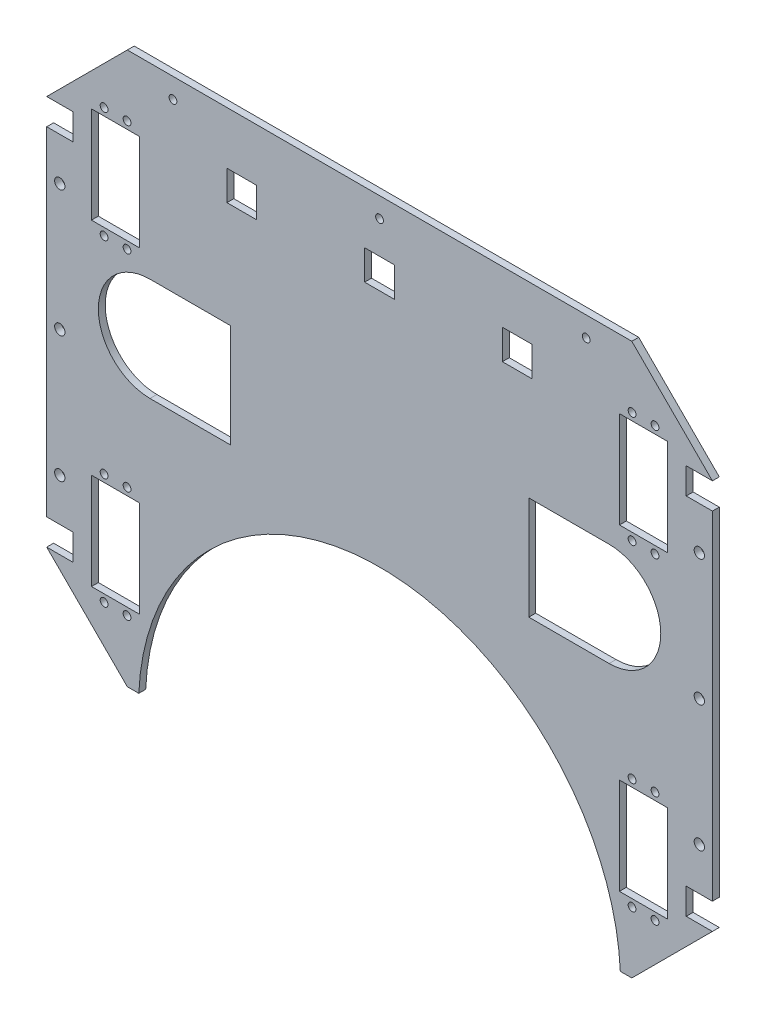
SolidWorks part; units mm, degrees
ref_plane "Plan de face" through (0, 0, 0) normal (0, 0, 1) x (1, 0, 0)
ref_plane "Plan de dessus" through (0, 0, 0) normal (0, 1, 0) x (1, 0, 0)
ref_plane "Plan de droite" through (0, 0, 0) normal (1, 0, 0) x (0, 0, -1)
sketch "Esquisse1" plane through (0, 0, 0) normal (0, 0, 1) x (1, 0, 0)
  line L0 (-145, 85) -> (-109.8862, 120.1138)
  line L1 (-109.8862, 120.1138) -> (-105, 125) construction
  line L2 (109.8862, 120.1138) -> (145, 85)
  line L3 (-85, 145) -> (85, 145) construction
  line L4 (105, -125) -> (109.8862, -120.1138) construction
  line L5 (-145, -145) -> (145, 145) construction
  line L6 (-145, 145) -> (145, -145) construction
  line L7 (85, 145) -> (105, 125) construction
  line L8 (-105, -125) -> (-85, -145) construction
  line L9 (-105, -125) -> (105, -125) construction
  line L10 (-105, 125) -> (105, 125) construction
  line L11 (85, -145) -> (105, -125) construction
  line L12 (-105, 125) -> (-85, 145) construction
  line L13 (105, 125) -> (109.8862, 120.1138) construction
  line L14 (-85, -145) -> (85, -145) construction
  line L15 (-109.8862, -120.1138) -> (-105, -125) construction
  line L16 (-109.8862, 120.1138) -> (109.8862, 120.1138)
  line L18 (-145, 0) -> (145, 0) construction
  line L19 (145, 85) -> (145, -85)
  line L20 (104.8862, -120.1138) -> (109.8862, -120.1138)
  line L21 (-109.8862, -120.1138) -> (-104.8862, -120.1138)
  line L22 (-145, 85) -> (-145, -85)
  line L24 (109.8862, -120.1138) -> (145, -85)
  line L25 (-145, -85) -> (-109.8862, -120.1138)
  line L28 (0, 125) -> (0, -125) construction
  arc A1 (-104.8862, -120.1138) -> (104.8862, -120.1138) centre (0, -125) cw
  point P0 (0, 0)
  point P30 (-145, 0)
  dimension "D1" = 290
  dimension "D2" = 290
  dimension "D6" = 60
  dimension "D7" = 60
extrude "Boss.-Extru.1" add sketch "Esquisse1" along normal blind 3
sketch "Esquisse21" plane through (0, 0, 3) normal (0, 0, 1) x (1, 0, 0)
  line L0 (0, 0) -> (191.7599, 0) construction
  line L1 (-145, 85) -> (-133.6, 85)
  line L2 (-145, 85) -> (-145, 73.6)
  line L3 (-145, 73.6) -> (-133.6, 73.6)
  line L4 (-133.6, 85) -> (-133.6, 73.6)
  line L5 (0, 0) -> (0, 158.3492) construction
  line L6 (145, 85) -> (145, 73.6)
  line L7 (145, 73.6) -> (133.6, 73.6)
  line L8 (133.6, 85) -> (133.6, 73.6)
  line L9 (145, 85) -> (133.6, 85)
  line L10 (-133.6, -85) -> (-133.6, -73.6)
  line L11 (-145, -73.6) -> (-133.6, -73.6)
  line L12 (-145, -85) -> (-145, -73.6)
  line L13 (-145, -85) -> (-133.6, -85)
  line L14 (145, -85) -> (145, -73.6)
  line L15 (145, -85) -> (133.6, -85)
  line L16 (145, -73.6) -> (133.6, -73.6)
  line L17 (133.6, -85) -> (133.6, -73.6)
  point P5 (-139.3, 79.3)
  point P9 (139.3, 79.3)
  point P19 (-139.3, -79.3)
  point P23 (139.3, -79.3)
  dimension "D1" = 11.4
  dimension "D2" = 11.4
  dimension "D3" = 5.7
  dimension "D4" = 5.7
sketch "Esquisse26" plane through (0, 0, 3) normal (0, 0, 1) x (1, 0, 0)
  line L0 (109.8862, 120.1138) -> (-109.8862, 120.1138) construction
  line L1 (-125.5, -48.1138) -> (-104.5, -48.1138)
  line L2 (-125.5, -48.1138) -> (-125.5, -90.1138)
  line L3 (-125.5, -90.1138) -> (-104.5, -90.1138)
  line L4 (-104.5, -48.1138) -> (-104.5, -90.1138)
  line L5 (-125.5, -48.1138) -> (-104.5, -90.1138) construction
  line L6 (-125.5, -90.1138) -> (-104.5, -48.1138) construction
  line L7 (145, -85) -> (145, 85) construction
  line L8 (-145, 85) -> (-145, -85) construction
  line L9 (-109.8862, -120.1138) -> (-104.8862, -120.1138) construction
  line L10 (104.8862, -120.1138) -> (109.8862, -120.1138) construction
  line L11 (-125.5, 90.1138) -> (-104.5, 90.1138)
  line L12 (-125.5, 90.1138) -> (-125.5, 48.1138)
  line L13 (-125.5, 48.1138) -> (-104.5, 48.1138)
  line L14 (-104.5, 90.1138) -> (-104.5, 48.1138)
  line L15 (-125.5, 90.1138) -> (-104.5, 48.1138) construction
  line L16 (-125.5, 48.1138) -> (-104.5, 90.1138) construction
  line L17 (104.5, 90.1138) -> (125.5, 90.1138)
  line L18 (104.5, 90.1138) -> (104.5, 48.1138)
  line L19 (104.5, 48.1138) -> (125.5, 48.1138)
  line L20 (125.5, 90.1138) -> (125.5, 48.1138)
  line L21 (104.5, 90.1138) -> (125.5, 48.1138) construction
  line L22 (104.5, 48.1138) -> (125.5, 90.1138) construction
  line L23 (104.5, -48.1138) -> (125.5, -48.1138)
  line L24 (104.5, -48.1138) -> (104.5, -90.1138)
  line L25 (104.5, -90.1138) -> (125.5, -90.1138)
  line L26 (125.5, -48.1138) -> (125.5, -90.1138)
  line L27 (104.5, -48.1138) -> (125.5, -90.1138) construction
  line L28 (104.5, -90.1138) -> (125.5, -48.1138) construction
  point P0 (-115, -69.1138)
  point P9 (-115, 69.1138)
  point P14 (115, 69.1138)
  point P19 (115, -69.1138)
  dimension "D1" = 30
  dimension "D2" = 30
  dimension "D3" = 42
  dimension "D4" = 21
  dimension "D5" = 30
  dimension "D6" = 30
  dimension "D7" = 42
  dimension "D8" = 21
  dimension "D9" = 30
  dimension "D10" = 30
  dimension "D11" = 42
  dimension "D12" = 21
  dimension "D13" = 21
  dimension "D14" = 42
  dimension "D15" = 30
  dimension "D16" = 30
extrude "Enlèv. mat.-Extru.1" cut sketch "Esquisse26" against normal through all
extrude "Enlèv. mat.-Extru.3" cut sketch "Esquisse21" against normal through all
sketch "Esquisse27" plane through (0, 0, 3) normal (0, 0, 1) x (1, 0, 0)
  line L0 (0, 120.1138) -> (0, -20) construction
  line L1 (109.8862, 120.1138) -> (-109.8862, 120.1138) construction
  line L2 (-145, 0) -> (145, 0) construction
  line L3 (-115, 90.1138) -> (-115, 48.1138) construction
  line L4 (-104.5, 90.1138) -> (-125.5, 90.1138) construction
  line L5 (-125.5, 48.1138) -> (-104.5, 48.1138) construction
  line L6 (-145, 73.6) -> (-145, -73.6) construction
  line L7 (145, -73.6) -> (145, 73.6) construction
  line L8 (-104.5, 48.1138) -> (-104.5, 90.1138) construction
  line L9 (-125.5, 90.1138) -> (-125.5, 48.1138) construction
  line L10 (-125.5, 69.1138) -> (-104.5, 69.1138) construction
  arc A0 (104.8862, -120.1138) -> (-104.8862, -120.1138) centre (0, -125) ccw construction
  point P0 (-120, 93.3138)
  point P1 (-110, 93.3138)
  point P2 (-120, 44.9138)
  point P3 (-110, 44.9138)
  point P29 (110, 44.9138)
  point P30 (120, 44.9138)
  point P31 (110, 93.3138)
  point P32 (120, 93.3138)
  point P33 (110, -44.9138)
  point P34 (120, -44.9138)
  point P35 (120, -93.3138)
  point P36 (110, -93.3138)
  point P37 (-110, -44.9138)
  point P38 (-120, -44.9138)
  point P39 (-110, -93.3138)
  point P40 (-120, -93.3138)
  dimension "D1" = 10
  dimension "D2" = 5
  dimension "D3" = 10
  dimension "D4" = 5
  dimension "D5" = 24.2
  dimension "D6" = 24.2
  dimension "D7" = 24.2
  dimension "D8" = 24.2
hole_wizard "Dégagement M32" positions "Esquisse31" profile "Esquisse30" hole size "M3" standard "ISO" end condition through all
sketch "Esquisse31" plane through (0, 0, 3) normal (0, 0, 1) x (1, 0, 0)
  point P1 (-120, 93.3138)
  point P4 (-110, 93.3138)
  point P7 (-120, 44.9138)
  point P10 (-110, 44.9138)
  point P13 (-120, -44.9138)
  point P16 (-110, -44.9138)
  point P19 (-120, -93.3138)
  point P22 (-110, -93.3138)
  point P25 (110, -93.3138)
  point P28 (120, -93.3138)
  point P31 (120, -44.9138)
  point P34 (110, -44.9138)
  point P37 (120, 44.9138)
  point P40 (110, 44.9138)
  point P43 (110, 93.3138)
  point P46 (120, 93.3138)
sketch "Esquisse30" plane through (-120, 93.3138, 3) normal (1, 0, 0) x (0, -1, 0)
  line L0 (0, 0) -> (0, 3)
  line L1 (0, 3) -> (1.7, 3)
  line L2 (1.7, 3) -> (1.7, 0)
  line L5 (1.7, 0) -> (0, 0)
  line L11 (0, -6.35) -> (0, 107.95) construction
  dimension "Diamètre du perçage jusqu'au prochain" = 3.4
  dimension "Profondeur du perçage jusqu'au prochain" = 3
sketch "Esquisse32" plane through (0, 0, 3) normal (0, 0, 1) x (1, 0, 0)
  line L0 (-118.5862, 111.4138) -> (118.5862, 111.4138) construction
  line L1 (-109.8862, 120.1138) -> (-145, 85) construction
  line L2 (145, 85) -> (109.8862, 120.1138) construction
  line L3 (-145, 73.6) -> (-133.6, 73.6) construction
  line L4 (-139.3, 73.6) -> (-139.3, -73.6) construction
  line L5 (-133.6, -73.6) -> (-145, -73.6) construction
  line L6 (139.3, 73.6) -> (139.3, -73.6) construction
  line L7 (133.6, 73.6) -> (145, 73.6) construction
  line L9 (109.8862, 120.1138) -> (-109.8862, 120.1138) construction
  point P18 (-139.3, 0)
  point P19 (-139.3, -55)
  point P20 (-139.3, 55)
  point P21 (-90, 111.4138)
  point P22 (0, 111.4138)
  point P23 (90, 111.4138)
  point P24 (139.3, 55)
  point P25 (139.3, 0)
  point P26 (139.3, -55)
  dimension "D1" = 8.7
  dimension "D2" = 55
  dimension "D3" = 55
  dimension "D4" = 55
  dimension "D5" = 55
  dimension "D6" = 90
  dimension "D7" = 90
hole_wizard "Dégagement M33" positions "Esquisse34" profile "Esquisse33" hole size "M3" standard "ISO" end condition through all
sketch "Esquisse34" plane through (0, 0, 3) normal (0, 0, 1) x (1, 0, 0)
  line L0 (-118.5862, 111.4138) -> (118.5862, 111.4138) construction
  point P10 (-90, 111.4138)
  point P13 (0, 111.4138)
  point P17 (90, 111.4138)
sketch "Esquisse33" plane through (-90, 111.4138, 3) normal (1, 0, 0) x (0, -1, 0)
  line L0 (0, 0) -> (0, 3)
  line L1 (0, 3) -> (1.7, 3)
  line L2 (1.7, 3) -> (1.7, 0)
  line L5 (1.7, 0) -> (0, 0)
  line L11 (0, -6.35) -> (0, 107.95) construction
  dimension "Diamètre du perçage jusqu'au prochain" = 3.4
  dimension "Profondeur du perçage jusqu'au prochain" = 3
sketch "Esquisse36" plane through (0, 0, 3) normal (0, 0, 1) x (1, 0, 0)
  line L0 (0, 0) -> (0, 131.833) construction
  line L1 (-145, 73.6) -> (-145, -73.6) construction
  line L2 (-109.8862, -120.1138) -> (-104.8862, -120.1138) construction
  line L3 (-100, -6.4138) -> (-65, -6.4138)
  line L4 (-65, -6.4138) -> (-65, 38.5862)
  line L5 (-65, 38.5862) -> (-100, 38.5862)
  line L6 (100, -6.4138) -> (65, -6.4138)
  line L7 (65, -6.4138) -> (65, 38.5862)
  line L8 (65, 38.5862) -> (100, 38.5862)
  arc A0 (100, 38.5862) -> (100, -6.4138) centre (100, 16.0862) cw
  arc A2 (-100, 38.5862) -> (-100, -6.4138) centre (-100, 16.0862) ccw
  dimension "D1" = 45
  dimension "D3" = 22.5
  dimension "D2" = 136.2
  dimension "D4" = 35
extrude "Enlèv. mat.-Extru.4" cut sketch "Esquisse36" against normal through all and the other way blind 10 contours L5 A2 L3 L4 | A0 L8 L7 L6
sketch "Esquisse37" plane through (0, 0, 0) normal (0, 0, -1) x (-1, 0, 0)
  line L0 (-139.3, 73.6) -> (-139.3, -73.6) construction
  line L1 (-133.6, 73.6) -> (-145, 73.6) construction
  line L2 (-145, -73.6) -> (-133.6, -73.6) construction
  line L4 (139.3, 73.6) -> (139.3, -73.6) construction
  line L5 (145, 73.6) -> (133.6, 73.6) construction
  line L6 (133.6, -73.6) -> (145, -73.6) construction
  point P6 (-139.3, 0)
  point P7 (-139.3, -55)
  point P8 (-139.3, 55)
  point P15 (139.3, 0)
  point P16 (139.3, 55)
  point P17 (139.3, -55)
  dimension "D1" = 55
  dimension "D2" = 55
  dimension "D3" = 55
  dimension "D4" = 55
hole_wizard "Dégagement M41" positions "Esquisse39" profile "Esquisse38" hole size "M4" standard "ISO" end condition through all
sketch "Esquisse39" plane through (0, 0, 0) normal (0, 0, -1) x (-1, 0, 0)
  point P1 (-139.3, 55)
  point P4 (-139.3, 0)
  point P7 (-139.3, -55)
  point P10 (139.3, 55)
  point P13 (139.3, 0)
  point P16 (139.3, -55)
sketch "Esquisse38" plane through (139.3, 55, 0) normal (1, 0, 0) x (0, 1, 0)
  line L0 (0, 0) -> (0, 3)
  line L1 (0, 3) -> (2.25, 3)
  line L2 (2.25, 3) -> (2.25, 0)
  line L5 (2.25, 0) -> (0, 0)
  line L11 (0, -6.35) -> (0, 107.95) construction
  dimension "Diamètre du perçage jusqu'au prochain" = 4.5
  dimension "Profondeur du perçage jusqu'au prochain" = 3
sketch "Esquisse40" plane through (0, 0, 3) normal (0, 0, 1) x (1, 0, 0)
  line L0 (-139.2862, 90.7138) -> (139.2862, 90.7138) construction
  line L1 (-109.8862, 120.1138) -> (-145, 85) construction
  line L2 (145, 85) -> (109.8862, 120.1138) construction
  line L3 (109.8862, 120.1138) -> (-109.8862, 120.1138) construction
  line L5 (-53.5, 97.2138) -> (-66.5, 97.2138)
  line L6 (-53.5, 97.2138) -> (-53.5, 84.2138)
  line L7 (-53.5, 84.2138) -> (-66.5, 84.2138)
  line L8 (-66.5, 97.2138) -> (-66.5, 84.2138)
  line L9 (-53.5, 97.2138) -> (-66.5, 84.2138) construction
  line L10 (-53.5, 84.2138) -> (-66.5, 97.2138) construction
  line L11 (6.5, 97.2138) -> (-6.5, 97.2138)
  line L12 (6.5, 97.2138) -> (6.5, 84.2138)
  line L13 (6.5, 84.2138) -> (-6.5, 84.2138)
  line L14 (-6.5, 97.2138) -> (-6.5, 84.2138)
  line L15 (6.5, 97.2138) -> (-6.5, 84.2138) construction
  line L16 (6.5, 84.2138) -> (-6.5, 97.2138) construction
  line L17 (66.5, 97.2138) -> (53.5, 97.2138)
  line L18 (66.5, 97.2138) -> (66.5, 84.2138)
  line L19 (66.5, 84.2138) -> (53.5, 84.2138)
  line L20 (53.5, 97.2138) -> (53.5, 84.2138)
  line L21 (66.5, 97.2138) -> (53.5, 84.2138) construction
  line L22 (66.5, 84.2138) -> (53.5, 97.2138) construction
  point P8 (0, 90.7138)
  point P9 (-60, 90.7138)
  point P10 (60, 90.7138)
  point P11 (-60, 90.7138)
  point P16 (0, 90.7138)
  point P21 (60, 90.7138)
  dimension "D1" = 29.4
  dimension "D2" = 60
  dimension "D3" = 60
  dimension "D4" = 13
  dimension "D5" = 13
  dimension "D6" = 13
  dimension "D7" = 13
  dimension "D8" = 13
  dimension "D9" = 13
extrude "Enlèv. mat.-Extru.5" cut sketch "Esquisse40" against normal through all
